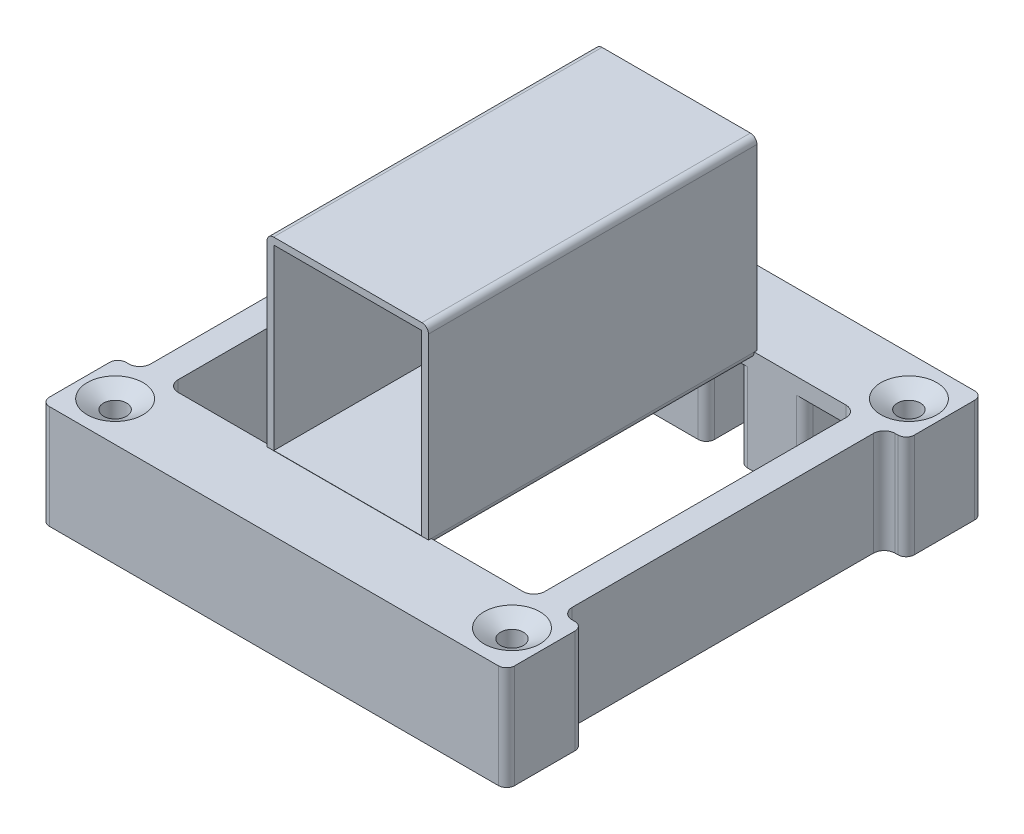
SolidWorks part; units mm, degrees
ref_plane "Front Plane" through (0, 0, 0) normal (0, 0, 1) x (1, 0, 0)
ref_plane "Top Plane" through (0, 0, 0) normal (0, 1, 0) x (1, 0, 0)
ref_plane "Right Plane" through (0, 0, 0) normal (1, 0, 0) x (0, 0, -1)
sketch "Sketch1" plane through (0, 0, 0) normal (0, 0, 1) x (1, 0, 0)
  line L0 (14.75, -16.3) -> (14.75, 16.3) construction
  line L1 (13.55, -17.5) -> (-13.55, -17.5) construction
  line L2 (-14.75, -16.3) -> (-14.75, 16.3) construction
  line L3 (13.55, 17.5) -> (-13.55, 17.5) construction
  line L4 (14.75, -16.3) -> (14.75, 16.3)
  line L5 (13.55, -17.5) -> (-13.55, -17.5)
  line L6 (-14.75, -16.3) -> (-14.75, 16.3)
  line L7 (13.55, 17.5) -> (-13.55, 17.5)
  line L8 (13.5, -16.25) -> (13.5, 16.25) construction
  line L9 (13.5, -16.25) -> (-13.5, -16.25) construction
  line L10 (-13.5, -16.25) -> (-13.5, 16.25) construction
  line L11 (13.5, 16.25) -> (-13.5, 16.25) construction
  line L12 (13.5, -16.25) -> (13.5, 16.25)
  line L13 (13.5, -16.25) -> (-13.5, -16.25)
  line L14 (-13.5, -16.25) -> (-13.5, 16.25)
  line L15 (13.5, 16.25) -> (-13.5, 16.25)
  arc A0 (14.75, 16.3) -> (13.55, 17.5) centre (13.55, 16.3) ccw construction
  arc A1 (13.55, -17.5) -> (14.75, -16.3) centre (13.55, -16.3) ccw construction
  arc A2 (-14.75, -16.3) -> (-13.55, -17.5) centre (-13.55, -16.3) ccw construction
  arc A3 (-13.55, 17.5) -> (-14.75, 16.3) centre (-13.55, 16.3) ccw construction
  arc A4 (14.75, 16.3) -> (13.55, 17.5) centre (13.55, 16.3) ccw
  arc A5 (13.55, -17.5) -> (14.75, -16.3) centre (13.55, -16.3) ccw
  arc A6 (-14.75, -16.3) -> (-13.55, -17.5) centre (-13.55, -16.3) ccw
  arc A7 (-13.55, 17.5) -> (-14.75, 16.3) centre (-13.55, 16.3) ccw
extrude "Boss-Extrude1" add sketch "Sketch1" along normal mid plane 60
sketch "Sketch2" plane through (0, 0, 0) normal (1, 0, 0) x (0, 0, -1)
  line L0 (-29.5, -24.25) -> (-29.5, 24.25) construction
  line L1 (-29.5, -16.3) -> (-43.5, -16.3)
  line L2 (-29.5, -16.3) -> (-29.5, -35.25)
  line L3 (-29.5, -35.25) -> (-43.5, -35.25)
  line L4 (-43.5, -16.3) -> (-43.5, -35.25)
  line L5 (-30, -16.3) -> (30, -16.3) construction
  line L6 (-29.5, -29.25) -> (29.5, -29.25) construction
  line L8 (-43.5, -15.125) -> (-43.5, 15.125) construction
  line L9 (0, 0) -> (0, -45.8115) construction
  line L10 (0, -15.125) -> (0, 15.125) construction
  line L11 (29.5, -35.25) -> (43.5, -35.25)
  line L12 (43.5, -16.3) -> (43.5, -35.25)
  line L13 (29.5, -16.3) -> (43.5, -16.3)
  line L14 (29.5, -16.3) -> (29.5, -35.25)
  dimension "D1" = 6
extrude "Boss-Extrude2" add sketch "Sketch2" along normal mid plane 85
sketch "Sketch3" plane through (0, -35.25, 0) normal (0, -1, 0) x (1, 0, 0)
  line L0 (0, 0) -> (59.8969, 0) construction
  line L1 (42.5, 29.5) -> (-42.5, 29.5) construction
  line L2 (-30, 29.5) -> (-24, 29.5)
  line L3 (-30, 29.5) -> (-30, 39.5)
  line L4 (-30, 39.5) -> (-24, 39.5)
  line L5 (-24, 29.5) -> (-24, 39.5)
  line L6 (-24.25, 29.5) -> (24.25, 29.5) construction
  line L7 (-12, 29.5) -> (-6, 29.5)
  line L8 (-12, 29.5) -> (-12, 39.5)
  line L9 (-12, 39.5) -> (-6, 39.5)
  line L10 (-6, 29.5) -> (-6, 39.5)
  line L11 (0, 0) -> (0, 46.5306) construction
  line L12 (30, 39.5) -> (24, 39.5)
  line L13 (24, 29.5) -> (24, 39.5)
  line L14 (30, 29.5) -> (24, 29.5)
  line L15 (30, 29.5) -> (30, 39.5)
  line L16 (12, 39.5) -> (6, 39.5)
  line L17 (6, 29.5) -> (6, 39.5)
  line L18 (12, 29.5) -> (6, 29.5)
  line L19 (12, 29.5) -> (12, 39.5)
  line L20 (12, -29.5) -> (12, -39.5)
  line L21 (12, -29.5) -> (6, -29.5)
  line L22 (6, -29.5) -> (6, -39.5)
  line L23 (12, -39.5) -> (6, -39.5)
  line L24 (30, -29.5) -> (30, -39.5)
  line L25 (30, -29.5) -> (24, -29.5)
  line L26 (24, -29.5) -> (24, -39.5)
  line L27 (30, -39.5) -> (24, -39.5)
  line L28 (-6, -29.5) -> (-6, -39.5)
  line L29 (-12, -39.5) -> (-6, -39.5)
  line L30 (-12, -29.5) -> (-12, -39.5)
  line L31 (-12, -29.5) -> (-6, -29.5)
  line L32 (-24, -29.5) -> (-24, -39.5)
  line L33 (-30, -39.5) -> (-24, -39.5)
  line L34 (-30, -29.5) -> (-30, -39.5)
  line L35 (-30, -29.5) -> (-24, -29.5)
  dimension "D1" = 12
  dimension "D2" = 12
  dimension "D3" = 6
  dimension "D4" = 6
  dimension "D5" = 10
extrude "Cut-Extrude1" cut sketch "Sketch3" against normal blind 16
fillet "Fillet1" radius 1.49 40 edges at (-24, -27.25, -39.5) (-6, -27.25, -39.5) (12, -27.25, -39.5) (30, -27.25, -39.5) (42.5, -25.775, -29.5) (42.5, -25.775, -43.5) (-42.5, -25.775, -43.5) (-42.5, -25.775, -29.5) (-30, -27.25, -29.5) (-30, -27.25, -39.5) (-24, -27.25, -29.5) (-12, -27.25, -29.5) (-12, -27.25, -39.5) (-6, -27.25, -29.5) (6, -27.25, -29.5) (6, -27.25, -39.5) (12, -27.25, -29.5) (24, -27.25, -29.5) (24, -27.25, -39.5) (30, -27.25, -29.5) (24, -27.25, 39.5) (6, -27.25, 39.5) (-12, -27.25, 39.5) (-30, -27.25, 39.5) (42.5, -25.775, 43.5) (42.5, -25.775, 29.5) (30, -27.25, 29.5) (30, -27.25, 39.5) (24, -27.25, 29.5) (12, -27.25, 29.5) (12, -27.25, 39.5) (6, -27.25, 29.5) (-6, -27.25, 29.5) (-6, -27.25, 39.5) (-12, -27.25, 29.5) (-24, -27.25, 29.5) (-24, -27.25, 39.5) (-30, -27.25, 29.5) (-42.5, -25.775, 43.5) (-42.5, -25.775, 29.5)
sketch "Sketch4" plane through (0, -16.3, 0) normal (0, 1, 0) x (1, 0, 0)
  line L0 (0, 0) -> (38.8928, 0) construction
  line L1 (-36.25, 36.25) -> (36.25, 36.25) construction
  line L2 (-36.25, 36.25) -> (-36.25, -36.25) construction
  line L3 (-36.25, -36.25) -> (36.25, -36.25) construction
  line L4 (36.25, 36.25) -> (36.25, -36.25) construction
  line L5 (-36.25, 36.25) -> (36.25, -36.25) construction
  line L6 (-36.25, -36.25) -> (36.25, 36.25) construction
  line L7 (0, 0) -> (0, -47.3346) construction
  circle A0 centre (36.25, -36.25) radius 2.1
  circle A1 centre (-36.25, -36.25) radius 2.1
  circle A2 centre (-36.25, 36.25) radius 2.1
  circle A3 centre (36.25, 36.25) radius 2.1
  point P0 (0, 0)
  dimension "D3" = 4.2
  dimension "D1" = 72.5
  dimension "D2" = 72.5
extrude "Cut-Extrude2" cut sketch "Sketch4" against normal through all both and the other way through all
chamfer "Chamfer1" distance 3 angle 30 4 edges at (36.25, -16.3, -38.35) (-36.25, -16.3, -38.35) (-36.25, -16.3, 34.15) (36.25, -16.3, 34.15) first distance on face at (36.25, -16.3, -38.35) first distance on face at (-36.25, -16.3, 34.15)
sketch "Sketch5" plane through (0, 0, -29.5) normal (0, 0, 1) x (1, 0, 0)
  line L0 (-14.75, -16.3) -> (-41.01, -16.3) construction
  line L1 (-38.5, -16.3) -> (-33.5, -16.3)
  line L2 (-38.5, -16.3) -> (-38.5, -35.25)
  line L3 (-38.5, -35.25) -> (-33.5, -35.25)
  line L4 (-33.5, -16.3) -> (-33.5, -35.25)
  line L5 (-31.49, -35.25) -> (-41.01, -35.25) construction
  line L6 (-42.5, -35.25) -> (-42.5, -16.3) construction
  line L7 (0, 0) -> (0, -37.6996) construction
  line L8 (33.5, -16.3) -> (33.5, -35.25)
  line L9 (38.5, -35.25) -> (33.5, -35.25)
  line L10 (38.5, -16.3) -> (38.5, -35.25)
  line L11 (38.5, -16.3) -> (33.5, -16.3)
  dimension "D1" = 4
  dimension "D2" = 5
extrude "Boss-Extrude3" add sketch "Sketch5" along normal up to surface (59 mm away) up to face at (0, -25.2999, 29.5)
fillet "Fillet2" radius 2 8 edges at (33.5, -25.775, 29.5) (38.5, -25.775, 29.5) (33.5, -25.775, -29.5) (38.5, -25.775, -29.5) (-38.5, -25.775, -29.5) (-33.5, -25.775, -29.5) (-33.5, -25.775, 29.5) (-38.5, -25.775, 29.5)
